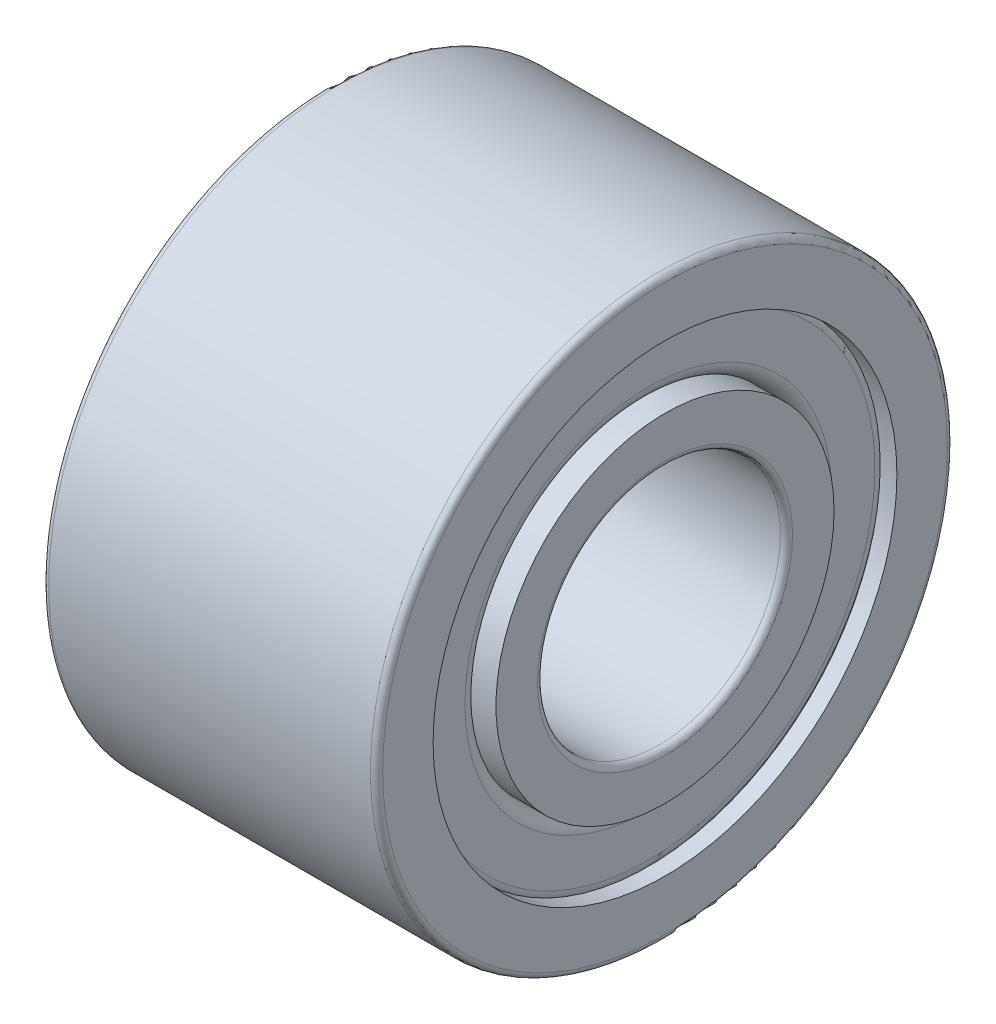
SolidWorks part; units mm, degrees
ref_plane "Plane1" through (0, 0, 0) normal (0, 0, 1) x (1, 0, 0)
ref_plane "Plane2" through (0, 0, 0) normal (0, 1, 0) x (1, 0, 0)
ref_plane "Plane3" through (0, 0, 0) normal (1, 0, 0) x (0, 0, -1)
sketch "Clipboard" plane through (0, 0, 0) normal (0, 0, 1) x (1, 0, 0)
  line L0 (-10, 0) -> (10, 0) construction
  line L1 (0, 0) -> (11.1282, -0.3886)
  line L2 (0, 0) -> (13.4918, 0.4711)
  line L3 (0, 0) -> (15.8553, -0.5537)
  line L4 (0, 0) -> (-22.3573, -0.3902)
  dimension "Race_OD" = 15.865
  dimension "Race_ID" = 11.135
sketch "OutRacSke" plane through (0, 0, 0) normal (0, 0, 1) x (1, 0, 0)
  line L0 (-4.95, 7.9325) -> (-4.95, 7.6369)
  line L1 (-4.95, 7.6369) -> (-5.5, 7.6369)
  line L2 (-5.5, 7.6369) -> (-5.5, 9.3)
  line L3 (-5.3, 9.5) -> (5.3, 9.5)
  line L4 (5.5, 9.3) -> (5.5, 7.6369)
  line L5 (5.5, 7.6369) -> (4.95, 7.6369)
  line L6 (4.95, 7.6369) -> (4.95, 7.9325)
  line L7 (4.95, 7.9325) -> (-4.95, 7.9325)
  line L8 (-7.9375, 0) -> (7.9375, 0) construction
  arc A0 (-5.5, 9.3) -> (-5.3, 9.5) centre (-5.3, 9.3) cw
  arc A1 (5.3, 9.5) -> (5.5, 9.3) centre (5.3, 9.3) cw
  dimension "D1" = 4.95
  dimension "Groove_Dp" = 0.2956
  dimension "Race_OD" = 15.865
  dimension "Cyl_Len" = 9.9
  dimension "halfWidth" = 5.5
revolve "OuterRace" add sketch "OutRacSke" angle 360 about L8 reverse direction yes
sketch "RolDetSke" plane through (0, 0, 0) normal (0, 0, 1) x (1, 0, 0)
  line L0 (-4.95, 7.4598) -> (-4.95, 6.75)
  line L1 (-4.95, 6.75) -> (4.95, 6.75)
  line L2 (4.95, 6.75) -> (4.95, 7.4598)
  line L3 (4.4768, 7.933) -> (-4.4768, 7.933)
  line L4 (-28.575, 6.75) -> (28.575, 6.75) construction
  arc A0 (4.95, 7.4598) -> (4.4768, 7.933) centre (4.4768, 7.4598) ccw
  arc A1 (-4.4768, 7.933) -> (-4.95, 7.4598) centre (-4.4768, 7.4598) ccw
  dimension "Cyl_Len" = 9.9
  dimension "radius" = 0.4732
  dimension "Roller_diameter" = 2.366
revolve "RollerDetailed" [suppressed] add sketch "RolDetSke" angle 360 about L4 reverse direction yes
ref_axis "Axis1" through (-50, 0, 0) along (1, 0, 0)
sketch "RolSimSke" plane through (0, 25.4, 0) normal (0, 0, 1) x (1, 0, 0)
  line L0 (-4.95, -17.9397) -> (-4.95, -19.3593)
  line L1 (-25.4, -25.4) -> (25.4, -25.4) construction
  line L2 (4.95, -19.3593) -> (4.95, -17.9397)
  line L3 (4.4768, -17.4665) -> (-4.4768, -17.4665)
  line L5 (4.4768, -19.8325) -> (-4.4768, -19.8325)
  arc A0 (4.95, -17.9397) -> (4.4768, -17.4665) centre (4.4768, -17.9397) ccw
  arc A1 (-4.4768, -17.4665) -> (-4.95, -17.9397) centre (-4.4768, -17.9397) ccw
  arc A2 (4.95, -19.3593) -> (4.4768, -19.8325) centre (4.4768, -19.3593) cw
  arc A3 (-4.4768, -19.8325) -> (-4.95, -19.3593) centre (-4.4768, -19.3593) cw
  dimension "Cyl_Len" = 9.9
  dimension "radius" = 0.4732
  dimension "Roller_diameter" = 2.366
revolve "RollersSimplified" add sketch "RolSimSke" angle 360 about L1
sketch "InsRacSke" plane through (0, 0, 0) normal (0, 0, 1) x (1, 0, 0)
  line L2 (-5.5, 5.5675) -> (-5.5, 4.2)
  line L4 (-5.3, 4) -> (5.3, 4)
  line L5 (5.5, 4.2) -> (5.5, 5.5675)
  line L8 (5.5, 5.5675) -> (-5.5, 5.5675)
  line L9 (-7.9375, 0) -> (7.9375, 0) construction
  arc A0 (-5.5, 4.2) -> (-5.3, 4) centre (-5.3, 4.2) ccw
  arc A2 (5.3, 4) -> (5.5, 4.2) centre (5.3, 4.2) ccw
  dimension "radius" = 0.2
  dimension "Bore" = 8
  dimension "halfWidth" = 5.5
  dimension "Race_ID" = 11.135
revolve "InnerRace" add sketch "InsRacSke" angle 360 about L9 reverse direction yes
sketch "CagSpiSke" plane through (0, 0, 0) normal (0, 0, 1) x (1, 0, 0)
  line L0 (-17.1595, 0) -> (17.1595, 0) construction
  line L3 (-5.225, 6.5134) -> (5.225, 6.5134)
  line L4 (-5.225, 6.5134) -> (-5.225, 6.9866)
  line L5 (-5.225, 6.9866) -> (5.225, 6.9866)
  line L6 (5.225, 6.5134) -> (5.225, 6.9866)
revolve "CageSpine" [suppressed] add sketch "CagSpiSke" angle 0.001 about L0
pattern_circular "RollersDetailed" [suppressed] count 2 every 180 about axis through (-50, 0, 0) along (1, 0, 0)
equation "\"halfWidth@OutRacSke\" =  \"Width@OutRacSke\" / 2"
equation "\"CLdia@Clipboard\" =  ( \"Race_OD@Clipboard\" + \"Race_ID@Clipboard\" )  / 2"
equation "\"CLRad@RolDetSke\" = ( \"Race_OD@Clipboard\" + \"Race_ID@Clipboard\" )  / 4"
equation "\"Roller_diameter@RolDetSke\" =  ( \"Race_OD@Clipboard\" -  \"Race_ID@Clipboard\" )  / 2 + .001"
equation "\"Roller_diameter@RolSimSke\" = ( \"Race_OD@Clipboard\" -  \"Race_ID@Clipboard\" )  / 2 + .001"
equation "\"radius@RolDetSke\" = \"Roller_diameter@RolDetSke\" / 5"
equation "\"radius@RolSimSke\" = \"Roller_diameter@RolSimSke\" / 5"
equation "\"Cyl_Len@OutRacSke\" = \"Cyl_Len@RolDetSke\""
equation "\"Cyl_Len@RolSimSke\" = \"Cyl_Len@RolDetSke\""
equation "\"halfCylLen@RolDetSke\" = \"Cyl_Len@RolDetSke\" / 2"
equation "\"D1@OutRacSke\" = \"Cyl_Len@OutRacSke\" / 2"
equation "\"cage_width@CagSpiSke\" =  ( \"Cyl_Len@RolDetSke\" + \"Width@OutRacSke\" )  / 2"
equation "\"halfwidth@CagSpiSke\" = \"cage_width@CagSpiSke\" / 2"
equation "\"cage_thickness@CagSpiSke\" = \"Roller_diameter@RolDetSke\" / 5"
equation "\"d2@CagSpiSke\" = \"CLRad@RolDetSke\" * 2 - \"cage_thickness@CagSpiSke\""
equation "\"Max_count@Clipboard\" = int( 3.14159265 / atn(( \"Roller_diameter@RolDetSke\" / 2) / sqr( \"CLRad@RolDetSke\"  *  \"CLRad@RolDetSke\" - ( \"Roller_diameter@RolDetSke\" / 2) *  ( \"Roller_diameter@RolDetSke\" / 2))))"
equation "\"Max_count@Clipboard\" = ((sgn( \"Max_count@Clipboard\" - \"Count@Clipboard\" )-1)*( \"Max_count@Clipboard\" - \"Count@Clipboard\" ))/-2+ \"Count@Clipboard\""
equation "\"Count@RollersDetailed\" = int( \"Show_count@Clipboard\" ) "
equation "\"Count@RollersDetailed\" = ((sgn( \"Count@RollersDetailed\" - \"Max_count@Clipboard\" )-1)*( \"Count@RollersDetailed\" - \"Max_count@Clipboard\" ))/-2+ \"Max_count@Clipboard\""
equation "\"Count@RollersDetailed\" = ((sgn( \"Count@RollersDetailed\" - \"Min_count@Clipboard\" )+1)*( \"Count@RollersDetailed\" - \"Min_count@Clipboard\"))/2 +\"Min_count@Clipboard\""
equation "\"Angle@RollersDetailed\" = 360.0 / \"Max_count@Clipboard\""
equation "\"Bore@RolSimSke\" = \"Race_ID@Clipboard\""
equation "\"Race_ID@InsRacSke\" = \"Race_ID@Clipboard\""
equation "\"halfWidth@InsRacSke\" = \"Width_IR@InsRacSke\" / 2"
equation "\"halfLength@RolSimSke\" = \"Cyl_Len@RolSimSke\" / 2"
equation "\"Race_OD@OutRacSke\" = \"Race_OD@Clipboard\""
equation "\"Width_IR@InsRacSke\" = \"Width@OutRacSke\""
equation "\"Angle@CageSpine\" =  \"Angle@RollersDetailed\" * ( \"Count@RollersDetailed\" -1 + int( \"Count@RollersDetailed\" / \"Max_count@Clipboard\" ) )  + 0.001 -  int( \"Count@RollersDetailed\" / \"Max_count@Clipboard\" ) * 0.001"
equation "\"Angle@CageSpine\" =  \"Angle@CageSpine\" * int( \"Min_count@Clipboard\" / 2) + int(1 / \"Min_count@Clipboard\")  * 0.001"
equation "\"radius@InsRacSke\" = \"Radius@OutRacSke\""
